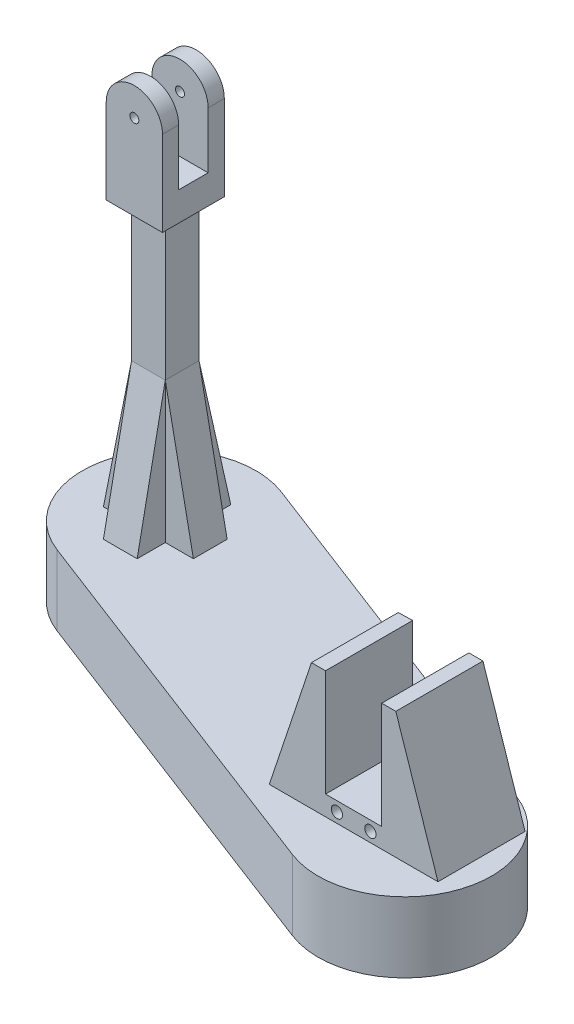
SolidWorks part; units mm, degrees
ref_plane "前基準面" through (0, 0, 0) normal (0, 0, 1) x (1, 0, 0)
ref_plane "上基準面" through (0, 0, 0) normal (0, 1, 0) x (1, 0, 0)
ref_plane "右基準面" through (0, 0, 0) normal (1, 0, 0) x (0, 0, -1)
sketch "草圖1" plane through (0, 0, 0) normal (0, 0, 1) x (1, 0, 0)
  line L0 (0, 0) -> (0, -11.05)
  line L1 (-10, 0) -> (-10, -30.2764)
  line L3 (10, -30.2764) -> (10, 0)
  line L4 (-10, -30.2764) -> (10, -30.2764)
  circle A1 centre (0, 0) radius 1.6
  arc A2 (10, 0) -> (-10, 0) centre (0, 0) ccw
  dimension "D1" = 11.05
  dimension "D2" = 3.2
  dimension "D3" = 20
extrude "填料-伸長1" add sketch "草圖1" along normal blind 12 contours L3 A2 L1 A1 region at (0, -11.2647, 0)
sketch "草圖2" plane through (10, 0, 0) normal (1, 0, 0) x (0, 0, -1)
  line L0 (-12, 0) -> (-9.1, 0)
  line L1 (-12, 0) -> (0, 0) construction
  line L2 (-12, 10) -> (-12, 0) construction
  line L3 (0, 0) -> (-2.9, 0)
  line L4 (-6, 0) -> (-3, 0)
  line L5 (-6, 0) -> (-9, 0)
  line L6 (-9, 0) -> (-9, 15.7808)
  line L7 (-9, 15.7808) -> (-3, 15.7808)
  line L8 (-3, 15.7808) -> (-3, 0)
  line L9 (-3, 0) -> (-3, -20)
  line L10 (-9, 0) -> (-8.6005, -20)
  line L11 (-8.6005, -20) -> (-3, -20)
  line M8 (0, 0) -> (-12, 0)
  dimension "D1" = 2.9
  dimension "D2" = 2.9
  dimension "D3" = 3
  dimension "D4" = 3
  dimension "D5" = 20
extrude "除料-伸長1" cut sketch "草圖2" against normal through all contours L8 L7 L6 M8 | L10 L11 L9 M8 region at (10, 7.8904, 6) region at (10, -9.8852, 5.9013)
sketch "草圖11" plane through (10, 0, 0) normal (1, 0, 0) x (0, 0, -1)
  line L0 (-9, 0) -> (-9, -20)
  line L1 (-9, -20) -> (-8.6005, -20)
  line L2 (-9, 0) -> (-8.6005, -20)
extrude "除料-伸長6" cut sketch "草圖11" against normal through all
sketch "草圖12" plane through (0, 0, 12) normal (0, 0, 1) x (1, 0, 0)
  line L0 (-10, 0) -> (-10, -30.2764)
  line L1 (-10, -30.2764) -> (10, -30.2764)
  line L2 (10, -30.2764) -> (10, 0)
  circle A0 centre (0, 0) radius 1.45
  circle A1 centre (0, 0) radius 10
  circle M1 centre (0, 0) radius 1.6
  line M2 (10, -30.2764) -> (10, 0)
  arc M3 (10, 0) -> (-10, 0) centre (0, 0) ccw
  line M4 (-10, 0) -> (-10, -30.2764)
  line M5 (-10, -30.2764) -> (10, -30.2764)
extrude "填料-伸長11" add sketch "草圖12" along normal blind 5 contours A1 M3 M1 | A1 M4 M5 M2 region at (0, -18.9541, 12) region at (0, 9.7172, 12)
sketch "草圖13" plane through (0, 0, 0) normal (0, 0, -1) x (-1, 0, 0)
  line L0 (-10, 0) -> (-10, -30.2764)
  line L1 (-10, -30.2764) -> (10, -30.2764)
  line L2 (10, 0) -> (10, -30.2764) construction
  line L3 (10, -30.2764) -> (-10, -30.2764) construction
  line L4 (10, -30.2764) -> (10, 0)
  circle A0 centre (0, 0) radius 1.45
  circle A1 centre (0, 0) radius 10
  circle M1 centre (0, 0) radius 1.6
  line M2 (-10, 0) -> (-10, -30.2764)
  line M3 (-10, -30.2764) -> (10, -30.2764)
  line M4 (10, -30.2764) -> (10, 0)
  arc M5 (10, 0) -> (-10, 0) centre (0, 0) ccw
extrude "填料-伸長12" add sketch "草圖13" along normal blind 5 contours A1 M5 M1 | A1 M2 M3 M4 region at (0, -18.9541, 0) region at (0, 9.7172, 0)
sketch "草圖14" plane through (-10, 0, 0) normal (-1, 0, 0) x (0, 0, 1)
  line L0 (3, -20) -> (0.96, -20)
  line L1 (0.96, -20) -> (0.96, 10)
  line L2 (3, 10) -> (-5, 10) construction
  line L3 (0.96, 10) -> (3, 10)
  line L5 (3, 10) -> (11.04, 10)
  line L6 (9, -20) -> (11.04, -20)
  line L7 (11.04, -20) -> (11.04, 10)
  line L8 (17, 10) -> (9, 10) construction
  line L9 (0.96, 10) -> (11.04, 10)
  line L10 (11.04, -20) -> (0.96, -20)
  line L11 (0.96, 10) -> (0.96, -20)
  line L12 (0.96, 10) -> (11.04, 10)
  line M7 (9, 0) -> (9, -20)
  line M8 (9, -20) -> (3, -20)
  line M9 (3, -20) -> (3, 0)
  line M10 (3, 0) -> (-5, 0)
  line M14 (17, 0) -> (9, 0)
  dimension "D1" = 2.04
  dimension "D2" = 2.04
extrude "除料-伸長7" cut sketch "草圖14" against normal through all contours L7 L5 L3 L1 M14 M10 M9 M8 M7 | L1 L0 M9 M10 | L6 L7 M14 M7 region at (-10, -3.1522, 6) region at (-10, -10, 1.98) region at (-10, -10, 10.02)
sketch "草圖15" plane through (0, -30.2764, 0) normal (0, -1, 0) x (1, 0, 0)
  line L0 (-10, 6) -> (10, 6)
  line L1 (-10, 17) -> (-10, -5) construction
  line L2 (10, 17) -> (10, -5) construction
  line L3 (0, 17) -> (0, -5)
  line L4 (-10, 17) -> (10, 17) construction
  line L5 (10, -5) -> (-10, -5) construction
  line L7 (-6, 0) -> (6, 0)
  line L8 (-6, 0) -> (-6, 12)
  line L9 (-6, 12) -> (6, 12)
  line L10 (6, 0) -> (6, 12)
  line L11 (-6, 0) -> (6, 12) construction
  line L12 (-6, 12) -> (6, 0) construction
  point P12 (0, 6)
  dimension "D1" = 12
  dimension "D2" = 12
extrude "填料-伸長13" add sketch "草圖15" along normal blind 100 contours L0 L10 L9 L3 | L9 L8 L0 L3 | L7 L10 L0 L3 | L8 L7 L3 L0 region at (-3, -30.2764, 9) region at (-3, -30.2764, 3) region at (3, -30.2764, 9) region at (3, -30.2764, 3)
sketch "草圖16" plane through (0, -130.2764, 0) normal (0, -1, 0) x (1, 0, 0)
  line L0 (0, 0) -> (0, 12)
  line L1 (-6, 0) -> (6, 0) construction
  line L2 (-6, 12) -> (6, 12) construction
  line L3 (0.1211, 6) -> (6, 6)
  line L4 (6, 0) -> (6, 12) construction
  line L5 (6, 6) -> (176, 6)
  line L10 (176, 6) -> (176, -54)
  line L11 (176, -54) -> (-61, -54)
  line L12 (-61, -54) -> (-61, 6)
  line L13 (-61, 6) -> (-61, 96)
  line L14 (-61, 96) -> (176, 96)
  line L15 (176, 96) -> (176, 6)
  line L16 (-6, 6) -> (-61, 6)
  line L17 (-6, 0) -> (-6, 12) construction
  point P10 (0, 6)
  line M6 (-6, 12) -> (-6, 0)
  line M7 (-6, 0) -> (6, 0)
  line M8 (6, 0) -> (6, 12)
  line M9 (6, 12) -> (-6, 12)
  dimension "D1" = 170
  dimension "D2" = 55
  dimension "D3" = 60
  dimension "D4" = 90
extrude "填料-伸長14" add sketch "草圖16" along normal blind 25 contours L16 L5 L15 L14 L13 M6 M9 M8 | L16 L12 L11 L10 L5 M6 M8 M7 | L0 M7 M9 M6 | L0 M7 M8 M9 region at (-3, -130.2764, 6) region at (57.7926, -130.2764, -24.1374) region at (0.0134, -130.2764, 6) region at (57.6948, -130.2764, 51.1423)
sketch "草圖17" plane through (0, 0, 12) normal (0, 0, 1) x (1, 0, 0)
  line L0 (0, 0) -> (0, -130.2764)
  line L1 (-6, -130.2764) -> (6, -130.2764) construction
sketch "草圖18" plane through (0, -130.2764, 0) normal (0, 1, 0) x (1, 0, 0)
  line L0 (0, -12) -> (116, -12)
  line L1 (116, -12) -> (137.15, -12)
  line L2 (116, -12) -> (94.85, -12)
  line L15 (0, -12) -> (100, -12)
  line L16 (100, -12) -> (100, -37)
  line L17 (100, -37) -> (90, -37)
  line L18 (100, -37) -> (110, -37)
  line L19 (90, -37) -> (90, -47)
  line L20 (90, -47) -> (110, -47)
  line L21 (110, -47) -> (110, -37)
  dimension "D1" = 100
  dimension "D2" = 25
  dimension "D3" = 10
  dimension "D4" = 10
  dimension "D5" = 10
sketch "草圖30" plane through (0, -130.2764, 0) normal (0, 1, 0) x (1, 0, 0)
  line L0 (0, -12) -> (129, -12)
  line L1 (116, -12) -> (137.15, -12) construction
  line L2 (129, -12) -> (129, -37)
  line L4 (129, -37) -> (139, -37)
  line L5 (129, -37) -> (119, -37)
  line L6 (119, -37) -> (119, -68)
  line L7 (119, -68) -> (139, -68)
  line L8 (139, -68) -> (139, -37)
  dimension "D1" = 129
  dimension "D2" = 10
  dimension "D3" = 10
  dimension "D4" = 31
extrude "填料-伸長19" add sketch "草圖30" along normal blind 7 contours L7 L8 L4 L5 L6 region at (129, -130.2764, 52.5)
sketch "草圖31" plane through (0, -130.2764, 0) normal (0, 1, 0) x (1, 0, 0)
  line L0 (119, -68) -> (114, -68)
  line L1 (114, -68) -> (114, -37.1297)
  line L2 (114, -37.1297) -> (119, -37)
  line L3 (119, -37) -> (119, -68)
  line L4 (139, -37) -> (139, -68)
  line L5 (139, -68) -> (144, -68)
  line L6 (144, -68) -> (144, -37)
  line L7 (144, -37) -> (139, -37)
  dimension "D1" = 5
  dimension "D2" = 5
extrude "填料-伸長20" add sketch "草圖31" along normal blind 45 contours L3 L0 L1 L2 | L7 L4 L5 L6
sketch "草圖33" plane through (0, 0, 68) normal (0, 0, 1) x (1, 0, 0)
  line L0 (114, -85.2764) -> (99, -130.2764)
  line L1 (0, -130.2764) -> (100, -130.2764) construction
  line L2 (99, -130.2764) -> (114, -130.2764)
  line L3 (0, -130.2764) -> (116, -130.2764) construction
  line L4 (116, -130.2764) -> (94.85, -130.2764) construction
  line L5 (114, -130.2764) -> (114, -85.2764)
  line L6 (144, -85.2764) -> (159, -130.2764)
  line L7 (-61, -130.2764) -> (176, -130.2764) construction
  line L8 (159, -130.2764) -> (144, -130.2764)
  line L9 (144, -85.2764) -> (144, -130.2764) construction
  line M4 (144, -130.2764) -> (144, -85.2764)
  line M10 (114, -85.2764) -> (114, -130.2764)
  dimension "D1" = 15
  dimension "D2" = 15
extrude "填料-伸長21" add sketch "草圖33" against normal blind 31 contours L8 L6 M4 | L0 L2 M10 region at (109, -115.2764, 68) region at (149, -115.2764, 68)
sketch "草圖35" plane through (0, 0, 37) normal (0, 0, -1) x (-1, 0, 0)
  line L0 (-139, -123.2764) -> (-139, -130.2764)
  line L1 (-119, -130.2764) -> (-159, -130.2764) construction
  line L2 (-139, -130.2764) -> (-119, -130.2764)
  line L3 (-119, -130.2764) -> (-119, -123.2764)
  line L4 (-119, -123.2764) -> (-139, -123.2764)
  line L5 (-139, -126.7764) -> (-119, -126.7764)
  line L6 (-129, -130.2764) -> (-129, -123.2764)
  circle A0 centre (-134.95, -126.7764) radius 2
  circle A1 centre (-123.05, -126.7764) radius 2
  point P15 (-129, -126.7764)
  dimension "D1" = 4
  dimension "D2" = 4
  dimension "D3" = 11.9
  dimension "D4" = 5.95
extrude "除料-伸長16" cut sketch "草圖35" against normal through all contours L5 A0 | L5 A0 | L5 A1 | L5 A1 region at (134.95, -125.9276, 37) region at (134.95, -127.6252, 37) region at (123.05, -125.9276, 37) region at (123.05, -127.6252, 37)
sketch "草圖37" plane through (0, -130.2764, 0) normal (0, 1, 0) x (1, 0, 0)
  line L0 (129, -68) -> (0, -68)
  line L1 (119, -68) -> (139, -68) construction
  dimension "D1" = 129
sketch "草圖38" plane through (-10, 0, 0) normal (-1, 0, 0) x (0, 0, 1)
  line L0 (0.96, 10) -> (0.76, 10)
  line L1 (0.96, 10) -> (-5, 10) construction
  line L2 (11.04, 10) -> (11.24, 10)
  line L3 (17, 10) -> (11.04, 10) construction
  line L4 (0.76, 10) -> (0.76, -20)
  line L5 (0.76, -20) -> (11.24, -20)
  line L6 (11.24, -20) -> (11.24, 10)
  line L7 (0.76, 10) -> (11.24, 10)
  line M3 (0.96, -20) -> (0.96, 0)
  line M4 (0.96, 0) -> (-5, 0)
  line M8 (17, 0) -> (11.04, 0)
  line M9 (11.04, 0) -> (11.04, -20)
  line M10 (11.04, -20) -> (0.96, -20)
  dimension "D1" = 0.2
  dimension "D2" = 0.2
extrude "除料-伸長18" cut sketch "草圖38" against normal through all contours L7 L0 L4 L6 L2 M4 M3 M10 M9 M8 | L4 L5 M3 M4 | L5 L6 M8 M9 region at (-10, -4.8695, 6) region at (-10, -10, 0.86) region at (-10, -10, 11.14)
fillet "圓角2" radius 10 4 edges at (176, -142.7764, -54) (176, -142.7764, 96) (-61, -142.7764, -54) (-61, -142.7764, 96)
sketch "草圖39" plane through (0, 0, 0) normal (0, 0, -1) x (-1, 0, 0)
  line L0 (-6, -80.2764) -> (-16, -130.2764)
  line L1 (-6, -130.2764) -> (-6, -30.2764) construction
  line L2 (0, -130.2764) -> (-116, -130.2764) construction
  line L3 (-16, -130.2764) -> (-6, -130.2764)
  line L4 (-6, -130.2764) -> (-6, -80.2764)
  line L6 (6, -80.2764) -> (16, -130.2764)
  line L7 (6, -130.2764) -> (6, -30.2764) construction
  line L8 (-166, -130.2764) -> (51, -130.2764) construction
  line L9 (16, -130.2764) -> (6, -130.2764)
  line L10 (6, -130.2764) -> (6, -80.2764)
  dimension "D1" = 50
  dimension "D2" = 10
  dimension "D3" = 10
extrude "填料-伸長22" add sketch "草圖39" against normal blind 12
sketch "草圖40" plane through (6, 0, 0) normal (1, 0, 0) x (0, 0, -1)
  line L0 (-12, -80.2764) -> (-22, -130.2764)
  line L1 (-12, -130.2764) -> (-37, -130.2764) construction
  line L2 (-22, -130.2764) -> (-12, -130.2764)
  line L3 (-12, 0) -> (-12, -130.2764) construction
  line L4 (-12, -130.2764) -> (-12, -80.2764)
  line L5 (0, -80.2764) -> (11.3032, -130.2764)
  line L6 (-86, -130.2764) -> (44, -130.2764) construction
  line L7 (11.3032, -130.2764) -> (0, -130.2764)
  line L8 (0, -130.2764) -> (0, -80.2764)
  dimension "D1" = 10
extrude "填料-伸長23" add sketch "草圖40" against normal blind 12
sketch "草圖43" plane through (0, -130.2764, 0) normal (0, 1, 0) x (1, 0, 0)
  line L0 (0, -4.6155) -> (135.9213, -56.7097) construction
  line L1 (11.053, 24.2233) -> (146.9743, -27.8709)
  line L2 (-11.053, -33.4544) -> (124.8684, -85.5486)
  line L4 (-74.976, 67.6441) -> (186.8952, 67.6441)
  line L5 (-74.976, 67.6441) -> (-74.976, -109.084)
  line L6 (-74.976, -109.084) -> (186.8952, -109.084)
  line L7 (186.8952, 67.6441) -> (186.8952, -109.084)
  arc A0 (11.053, 24.2233) -> (-11.053, -33.4544) centre (0, -4.6155) ccw
  arc A1 (124.8684, -85.5486) -> (146.9743, -27.8709) centre (135.9213, -56.7097) ccw
  point P2 (67.9607, -30.6626)
extrude "除料-伸長19" cut sketch "草圖43" against normal through all
